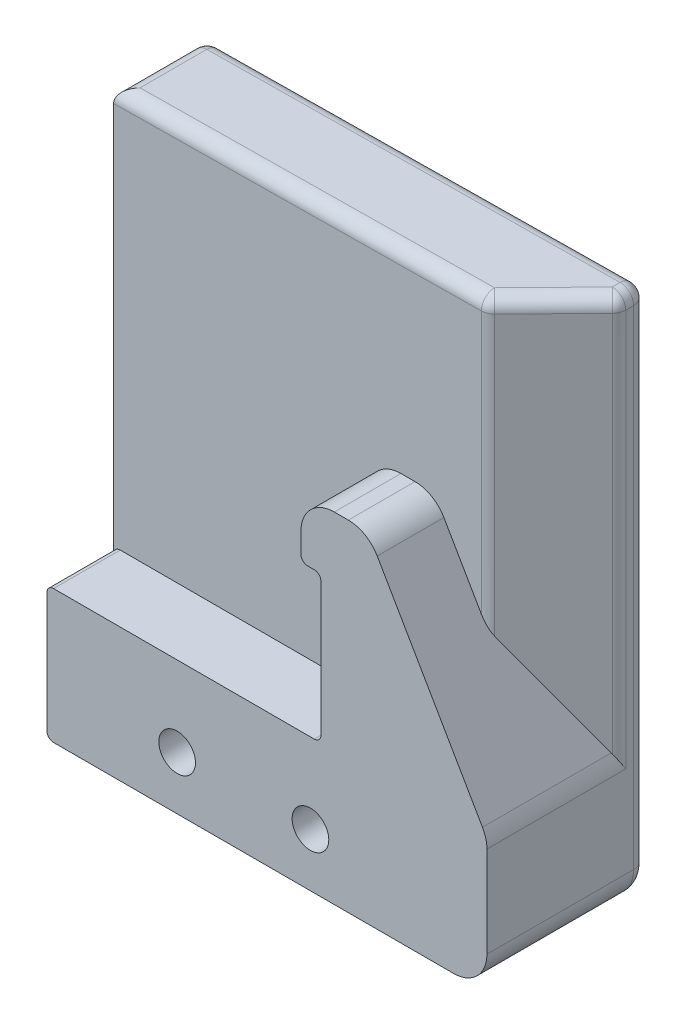
SolidWorks part; units mm, degrees
ref_plane "Front Plane" through (0, 0, 0) normal (0, 0, 1) x (1, 0, 0)
ref_plane "Top Plane" through (0, 0, 0) normal (0, 1, 0) x (1, 0, 0)
ref_plane "Right Plane" through (0, 0, 0) normal (1, 0, 0) x (0, 0, -1)
sketch "Sketch1" plane through (0, 0, 0) normal (0, 0, 1) x (1, 0, 0)
  line L3 (-66, 20) -> (-24.8979, 20)
  line L4 (-24.8979, 20) -> (-24.8979, 42)
  line L5 (-24.8979, 42) -> (-27.8979, 42)
  line L6 (-27.8979, 42) -> (-27.8979, 51)
  line L7 (-27.8979, 51) -> (-17.8979, 51)
  line L8 (-17.8979, 51) -> (0, 20)
  line L9 (0, 20) -> (0, 0)
  line L10 (0, 0) -> (-66, 0)
  line L11 (-66, 20) -> (-66, 0)
  dimension "D1" = 66
  dimension "D2" = 10
  dimension "D3" = 9
  dimension "D4" = 3
  dimension "D5" = 22
  dimension "D6" = 20
  dimension "D7" = 30
extrude "Boss-Extrude1" add sketch "Sketch1" along normal blind 10
fillet "Fillet1" radius 5 4 edges at (0, 0, 5) (0, 20, 5) (-17.8979, 51, 5) (-27.8979, 51, 5)
fillet "Fillet2" radius 1 5 edges at (-24.8979, 20, 5) (-24.8979, 42, 5) (-27.8979, 42, 5) (-66, 0, 5) (-66, 20, 5)
hole_wizard "M5 Clearance Hole1" positions "Sketch2" profile "Sketch3" hole size "M5" standard "ISO" end condition through all
sketch "Sketch2" plane through (0, 0, 10) normal (0, 0, 1) x (1, 0, 0)
  line L0 (-65, 0) -> (-5, 0) construction
  line L1 (0, 5) -> (0, 18.6603) construction
  point P0 (-26.47, 8)
  point P2 (-46.47, 8)
  dimension "D1" = 8
  dimension "D2" = 20
  dimension "D3" = 26.47
sketch "Sketch3" plane through (-26.47, 8, 10) normal (1, 0, 0) x (0, -1, 0)
  line L0 (0, 0) -> (0, 10)
  line L1 (0, 10) -> (2.75, 10)
  line L2 (2.75, 10) -> (2.75, 0)
  line L5 (2.75, 0) -> (0, 0)
  line L11 (0, -6.35) -> (0, 107.95) construction
  dimension "Thru Hole Dia." = 5.5
  dimension "Thru Hole Depth" = 10
sketch "Sketch4" plane through (0, 0, 0) normal (0, 0, -1) x (-1, 0, 0)
  line L0 (66, 19) -> (66, 1) construction
  line L1 (65, 0) -> (5, 0) construction
  line L2 (0, 5) -> (0, 18.6603) construction
  line L3 (66, 19) -> (66, 1)
  line L4 (65, 0) -> (5, 0)
  line L5 (0, 5) -> (0, 18.6603)
  line L6 (0, 18.6603) -> (0, 80.2757)
  line L7 (0, 80.2757) -> (66, 79.5163)
  line L8 (66, 79.5163) -> (66, 19)
  arc A0 (65, 0) -> (66, 1) centre (65, 1) ccw construction
  arc A1 (0, 5) -> (5, 0) centre (5, 5) ccw construction
  arc A2 (65, 0) -> (66, 1) centre (65, 1) ccw
  arc A3 (0, 5) -> (5, 0) centre (5, 5) ccw
extrude "Boss-Extrude2" add sketch "Sketch4" along normal blind 14
chamfer "Chamfer1" distance 10 angle 45 1 edges at (0, 49.468, 0)
fillet "Fillet4" radius 2 12 edges at (-66, 40.2582, -14) (-65.7071, 0.2929, -14) (-35, 0, -14) (0, 80.2757, -12) (-5, 80.2182, -5) (-38, 79.8385, 0) (-66, 79.5163, -7) (-33, 79.896, -14) (-1.4645, 1.4645, -14) (0, 42.6379, -14) (0, 49.468, -10) (-10, 58.7406, 0)
